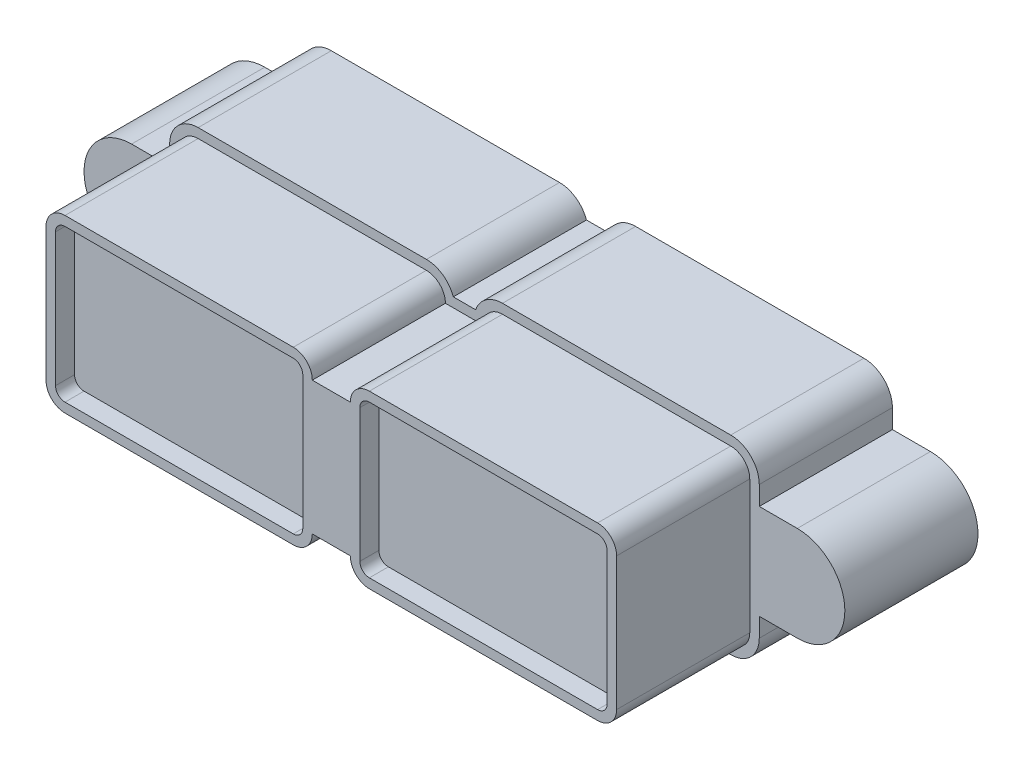
SolidWorks part; units mm, degrees
ref_plane "Front Plane" through (0, 0, 0) normal (0, 0, 1) x (1, 0, 0)
ref_plane "Top Plane" through (0, 0, 0) normal (0, 1, 0) x (1, 0, 0)
ref_plane "Right Plane" through (0, 0, 0) normal (1, 0, 0) x (0, 0, -1)
sketch "Sketch1" plane through (0, 0, 0) normal (0, 0, 1) x (1, 0, 0)
  line L1 (-22.5, 18.75) -> (22.5, 18.75)
  line L2 (-22.5, 18.75) -> (-22.5, -18.75)
  line L3 (-22.5, -18.75) -> (22.5, -18.75)
  line L4 (22.5, 18.75) -> (22.5, -18.75)
  line L5 (-22.5, 18.75) -> (22.5, -18.75) construction
  line L6 (-22.5, -18.75) -> (22.5, 18.75) construction
  point P0 (0, 0)
  dimension "D1" = 37.5
  dimension "D2" = 45
extrude "Boss-Extrude1" add sketch "Sketch1" along normal blind 2
sketch "Sketch2" plane through (0, 0, 2) normal (0, 0, 1) x (1, 0, 0)
  line L0 (0, 18.75) -> (0, -18.75) construction
  line L1 (22.5, 18.75) -> (-22.5, 18.75) construction
  line L2 (-22.5, -18.75) -> (22.5, -18.75) construction
  line L4 (-20, -4.75) -> (20, -4.75)
  line L5 (-20, -4.75) -> (-20, -17.75)
  line L6 (-20, -17.75) -> (20, -17.75)
  line L7 (20, -4.75) -> (20, -17.75)
  line L8 (-20, -4.75) -> (20, -17.75) construction
  line L9 (-20, -17.75) -> (20, -4.75) construction
  point P6 (0, -11.25)
  dimension "D1" = 13
  dimension "D2" = 40
  dimension "D3" = 1
extrude "Boss-Extrude2" add sketch "Sketch2" along normal blind 7
sketch "Sketch3" plane through (0, 0, 9) normal (0, 0, 1) x (1, 0, 0)
  line L0 (0, -4.75) -> (0, -17.75) construction
  line L1 (20, -4.75) -> (-20, -4.75) construction
  line L2 (-20, -17.75) -> (20, -17.75) construction
  line L3 (-1, -7.75) -> (-1, -6.75)
  line L4 (1, -6.75) -> (15, -6.75)
  line L5 (1, -7.75) -> (1, -6.75)
  line L6 (1, -15.75) -> (15, -15.75)
  line L7 (15, -6.75) -> (15, -15.75)
  line L8 (-1, -6.75) -> (-15, -6.75)
  line L9 (1, -14.75) -> (1, -15.75)
  line L10 (-1, -15.75) -> (-15, -15.75)
  line L11 (-15, -6.75) -> (-15, -15.75)
  line L12 (1, -7.75) -> (-1, -7.75)
  line L13 (-1, -14.75) -> (-1, -15.75)
  line L14 (1, -14.75) -> (-1, -14.75)
  line L15 (-20, -17.75) -> (20, -17.75) construction
  point P20 (0, -7.75)
  point P24 (0, -14.75)
  dimension "D1" = 2
  dimension "D2" = 2
  dimension "D3" = 30
  dimension "D5" = 2
  dimension "D6" = 1
  dimension "D7" = 1
extrude "Boss-Extrude3" add sketch "Sketch3" along normal blind 7
fillet "Fillet1" radius 1 8 edges at (-15, -15.75, 12.5) (-1, -15.75, 12.5) (1, -15.75, 12.5) (-15, -6.75, 12.5) (15, -15.75, 12.5) (15, -6.75, 12.5) (1, -6.75, 12.5) (-1, -6.75, 12.5)
sketch "Sketch4" plane through (0, 0, 16) normal (0, 0, 1) x (1, 0, 0)
  line L0 (-1.5, -14.75) -> (-1.5, -7.75)
  line L1 (1.5, -7.75) -> (1.5, -14.75)
  line L48 (-14.5, -7.75) -> (-14.5, -14.75)
  line L49 (-14, -15.25) -> (-2, -15.25)
  line L51 (-2, -14.25) -> (2, -14.25)
  line L53 (2, -15.25) -> (14, -15.25)
  line L54 (14.5, -14.75) -> (14.5, -7.75)
  line L55 (14, -7.25) -> (2, -7.25)
  line L57 (2, -8.25) -> (-2, -8.25)
  line L59 (-2, -7.25) -> (-14, -7.25)
  line L60 (-14.5, -7.75) -> (-14.5, -14.75)
  line L61 (-14, -15.25) -> (-2, -15.25)
  line L65 (2, -15.25) -> (14, -15.25)
  line L66 (14.5, -14.75) -> (14.5, -7.75)
  line L67 (14, -7.25) -> (2, -7.25)
  line L71 (-2, -7.25) -> (-14, -7.25)
  arc A32 (-14.5, -14.75) -> (-14, -15.25) centre (-14, -14.75) ccw
  arc A33 (-2, -15.25) -> (-2, -14.25) centre (-2, -14.75) ccw
  arc A34 (2, -14.25) -> (2, -15.25) centre (2, -14.75) ccw
  arc A35 (14, -15.25) -> (14.5, -14.75) centre (14, -14.75) ccw
  arc A36 (14.5, -7.75) -> (14, -7.25) centre (14, -7.75) ccw
  arc A37 (2, -7.25) -> (2, -8.25) centre (2, -7.75) ccw
  arc A38 (-2, -8.25) -> (-2, -7.25) centre (-2, -7.75) ccw
  arc A39 (-14, -7.25) -> (-14.5, -7.75) centre (-14, -7.75) ccw
  arc A40 (-14.5, -14.75) -> (-14, -15.25) centre (-14, -14.75) ccw
  arc A41 (-2, -15.25) -> (-1.5, -14.75) centre (-2, -14.75) ccw
  arc A42 (1.5, -14.75) -> (2, -15.25) centre (2, -14.75) ccw
  arc A43 (14, -15.25) -> (14.5, -14.75) centre (14, -14.75) ccw
  arc A44 (14.5, -7.75) -> (14, -7.25) centre (14, -7.75) ccw
  arc A45 (2, -7.25) -> (1.5, -7.75) centre (2, -7.75) ccw
  arc A46 (-1.5, -7.75) -> (-2, -7.25) centre (-2, -7.75) ccw
  arc A47 (-14, -7.25) -> (-14.5, -7.75) centre (-14, -7.75) ccw
  dimension "D1" = 0.5
extrude "Cut-Extrude1" cut sketch "Sketch4" against normal blind 1
sketch "Sketch5" plane through (0, 0, 9) normal (0, 0, 1) x (1, 0, 0)
  line L11 (-20, -4.75) -> (-20, -17.75) construction
  line L12 (20, -17.75) -> (20, -4.75) construction
  line L15 (-15.5, -7.75) -> (-15.5, -14.75)
  line L26 (-15.5, -7.75) -> (-15.5, -14.75) construction
  line L27 (-17.5, -8.75) -> (-15.5, -8.75)
  line L28 (15.5, -14.75) -> (15.5, -7.75)
  line L29 (15.5, -14.75) -> (15.5, -7.75) construction
  line L30 (-15.5, -8.75) -> (-15.5, -7.75)
  line L31 (-17.5, -13.75) -> (-15.5, -13.75)
  line L32 (-15.5, -13.75) -> (-15.5, -14.75)
  line L33 (17.5, -13.75) -> (15.5, -13.75)
  line L34 (15.5, -13.75) -> (15.5, -14.75)
  line L35 (17.5, -8.75) -> (15.5, -8.75)
  line L36 (15.5, -8.75) -> (15.5, -7.75)
  line L41 (14, -6.25) -> (2, -6.25)
  line L42 (-2, -6.25) -> (-14, -6.25)
  line L43 (0.5858, -7.25) -> (-0.5858, -7.25)
  line L44 (14, -6.25) -> (2, -6.25)
  line L45 (-2, -6.25) -> (-14, -6.25)
  line L46 (0.5858, -7.25) -> (-0.5858, -7.25)
  line L51 (20.5, -18.25) -> (20.5, -4.25)
  line L52 (-20.5, -18.25) -> (20.5, -18.25)
  line L53 (-20.5, -4.25) -> (-20.5, -18.25)
  line L54 (20.5, -4.25) -> (-20.5, -4.25)
  line L55 (20.5, -18.25) -> (20.5, -4.25)
  line L56 (-20.5, -18.25) -> (20.5, -18.25)
  line L57 (-20.5, -4.25) -> (-20.5, -18.25)
  line L58 (20.5, -4.25) -> (-20.5, -4.25)
  line L65 (2, -16.25) -> (14, -16.25)
  line L66 (-14, -16.25) -> (-2, -16.25)
  line L67 (-0.5858, -15.25) -> (0.5858, -15.25)
  line L68 (2, -16.25) -> (14, -16.25)
  line L69 (-14, -16.25) -> (-2, -16.25)
  line L70 (-0.5858, -15.25) -> (0.5858, -15.25)
  circle A4 centre (-17.5, -11.25) radius 2.5 construction
  circle A5 centre (17.5, -11.25) radius 2.5 construction
  arc A14 (-15.5, -14.75) -> (-14, -16.25) centre (-14, -14.75) ccw
  arc A15 (-14, -6.25) -> (-15.5, -7.75) centre (-14, -7.75) ccw
  arc A16 (-15.5, -14.75) -> (-14, -16.25) centre (-14, -14.75) ccw
  arc A17 (-14, -6.25) -> (-15.5, -7.75) centre (-14, -7.75) ccw
  arc A18 (-17.5, -13.75) -> (-17.5, -8.75) centre (-17.5, -11.25) cw
  arc A19 (17.5, -8.75) -> (17.5, -13.75) centre (17.5, -11.25) cw
  arc A20 (14, -16.25) -> (15.5, -14.75) centre (14, -14.75) ccw
  arc A21 (15.5, -7.75) -> (14, -6.25) centre (14, -7.75) ccw
  arc A22 (14, -16.25) -> (15.5, -14.75) centre (14, -14.75) ccw
  arc A23 (15.5, -7.75) -> (14, -6.25) centre (14, -7.75) ccw
  arc A32 (2, -6.25) -> (0.5858, -7.25) centre (2, -7.75) ccw
  arc A33 (-0.5858, -7.25) -> (-2, -6.25) centre (-2, -7.75) ccw
  arc A34 (2, -6.25) -> (0.5858, -7.25) centre (2, -7.75) ccw
  arc A35 (-0.5858, -7.25) -> (-2, -6.25) centre (-2, -7.75) ccw
  arc A41 (0.5858, -15.25) -> (2, -16.25) centre (2, -14.75) ccw
  arc A42 (-2, -16.25) -> (-0.5858, -15.25) centre (-2, -14.75) ccw
  arc A43 (0.5858, -15.25) -> (2, -16.25) centre (2, -14.75) ccw
  arc A44 (-2, -16.25) -> (-0.5858, -15.25) centre (-2, -14.75) ccw
  point P13 (-20, -11.25)
  dimension "D3" = 5
  dimension "D4" = 0.5
  dimension "D5" = 0.5
  dimension "D6" = 0.5
  dimension "D7" = 0.5
  dimension "D8" = 0.5
extrude "Cut-Extrude2" cut sketch "Sketch5" against normal up to surface (7 mm away) up to face at (0, 0, 2)
sketch "Sketch6" plane through (0, 0, 0) normal (0, 0, -1) x (-1, 0, 0)
  line L0 (0, 18.75) -> (0, -18.75) construction
  line L1 (-22.5, 18.75) -> (22.5, 18.75) construction
  line L2 (22.5, -18.75) -> (-22.5, -18.75) construction
  line L3 (-0.5, 18.25) -> (-0.5, -1.75)
  line L4 (-11.5, 18.25) -> (11.5, 18.25) construction
  line L5 (-11.5, 18.25) -> (-11.5, -1.75)
  line L6 (-11.5, -1.75) -> (11.5, -1.75) construction
  line L7 (11.5, 18.25) -> (11.5, -1.75)
  line L8 (-11.5, 18.25) -> (11.5, -1.75) construction
  line L9 (-11.5, -1.75) -> (11.5, 18.25) construction
  line L10 (-0.5, -1.75) -> (-11.5, -1.75)
  line L11 (-11.5, 18.25) -> (-0.5, 18.25)
  line L12 (11.5, 18.25) -> (0.5, 18.25)
  line L13 (0.5, 18.25) -> (0.5, -1.75)
  line L14 (0.5, -1.75) -> (11.5, -1.75)
  point P6 (0, 8.25)
  dimension "D1" = 20
  dimension "D2" = 23
  dimension "D3" = 11
  dimension "D4" = 0.5
extrude "Boss-Extrude5" add sketch "Sketch6" along normal blind 12
sketch "Sketch7" plane through (0, 18.25, 0) normal (0, 1, 0) x (1, 0, 0)
  line L0 (-11.5, 12) -> (-0.5, 12) construction
  line L1 (-10.5, 10) -> (-1.5, 10)
  line L2 (-10.5, 10) -> (-10.5, 1)
  line L3 (-10.5, 1) -> (-1.5, 1)
  line L4 (-1.5, 10) -> (-1.5, 1)
  line L5 (1.5, 10) -> (10.5, 10)
  line L6 (1.5, 10) -> (1.5, 1)
  line L7 (1.5, 1) -> (10.5, 1)
  line L8 (10.5, 10) -> (10.5, 1)
  line L9 (-11.5, 12) -> (-11.5, 0) construction
  line L10 (-0.5, 12) -> (-0.5, 0) construction
  line L11 (0.5, 12) -> (0.5, 0) construction
  line L12 (0.5, 0) -> (11.5, 0) construction
  dimension "D1" = 2
  dimension "D2" = 1
  dimension "D3" = 1
  dimension "D4" = 1
  dimension "D5" = 1
extrude "Cut-Extrude3" cut sketch "Sketch7" against normal blind 12
sketch "Sketch8" plane through (0, 0, 2) normal (0, 0, 1) x (1, 0, 0)
  line L1 (66.4152, 48.3377) -> (-66.4152, 48.3377)
  line L2 (66.4152, 48.3377) -> (66.4152, -48.3377)
  line L3 (66.4152, -48.3377) -> (-66.4152, -48.3377)
  line L4 (-66.4152, 48.3377) -> (-66.4152, -48.3377)
  line L5 (66.4152, 48.3377) -> (-66.4152, -48.3377) construction
  line L6 (66.4152, -48.3377) -> (-66.4152, 48.3377) construction
  point P0 (0, 0)
extrude "Cut-Extrude4" cut sketch "Sketch8" against normal blind 20
